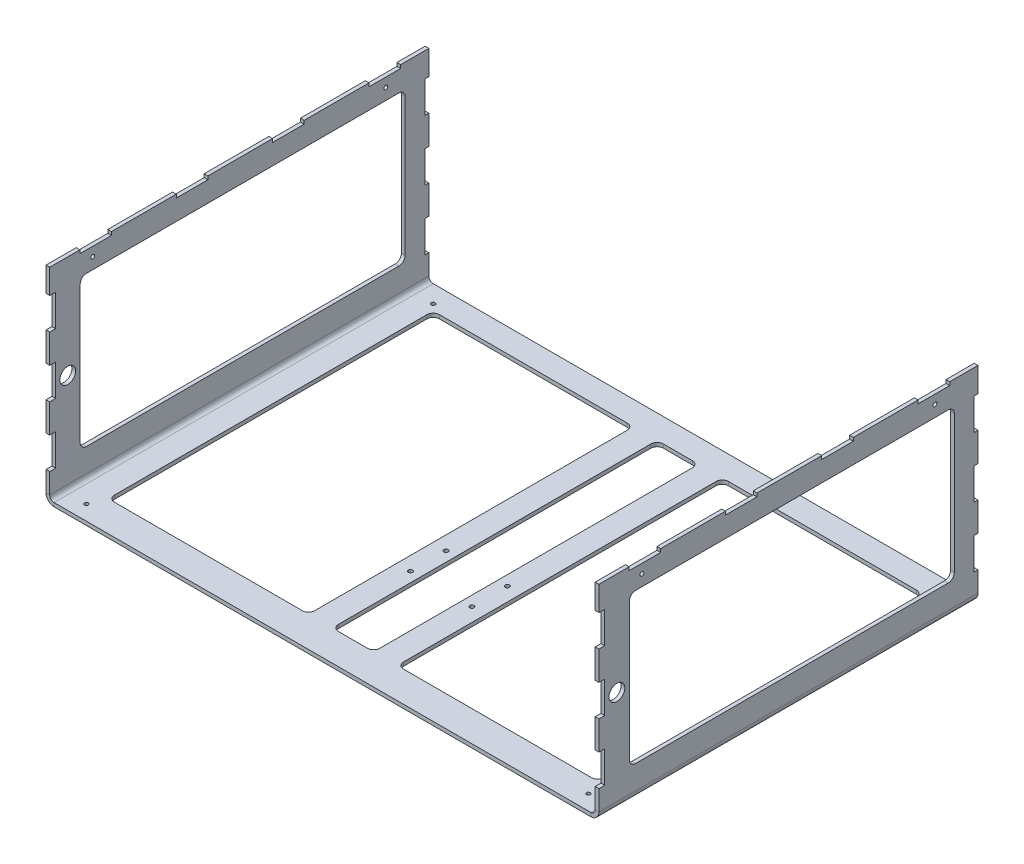
SolidWorks part; units mm, degrees
note: The reader was unsure of these and kept them because the rebuilt part matched: thickness of "Base-Flange1", "Edge-Flange1", "Edge-Flange2", "Sheet-Metal2", "Sheet-Metal3", "Sheet-Metal4", "Sheet-Metal5", "Sheet-Metal6", "Sheet-Metal11", "Sheet-Metal12", "Sheet-Metal13", "Sheet-Metal14", "Sheet-Metal15", "Sheet-Metal16", "Sheet-Metal17", "Sheet-Metal18", "Sheet-Metal21", "Sheet-Metal22"; flange length of "Edge-Flange1", "Edge-Flange2".
material "5052-H34"
ref_plane "Front Plane" through (0, 0, 0) normal (0, 0, 1) x (1, 0, 0)
ref_plane "Top Plane" through (0, 0, 0) normal (0, 1, 0) x (1, 0, 0)
ref_plane "Right Plane" through (0, 0, 0) normal (1, 0, 0) x (0, 0, -1)
sketch "Sketch1" plane through (0, 0, 0) normal (0, 1, 0) x (1, 0, 0)
  line L1 (-222.25, 152.4) -> (222.25, 152.4)
  line L2 (-222.25, 152.4) -> (-222.25, -152.4)
  line L3 (-222.25, -152.4) -> (222.25, -152.4)
  line L4 (222.25, 152.4) -> (222.25, -152.4)
  point P4 (0, 152.4)
  point P6 (222.25, 0)
  dimension "D1" = 444.5
  dimension "D2" = 304.8
base flange "Base-Flange1" sketch "Sketch1" thickness 3 reverse thickness direction no parameters "D1"=0.7366
edge flange "Edge-Flange1" sketch "Sketch11" flange angle 90 flange length 165.1 flange position material inside bend radius 3.5 thickness 3 relief rectangular parameters "D6"=10
sketch "Sketch11" plane through (-222.25, 0, 0) normal (-1, 0, 0) x (0, 0, 1)
  line L0 (-152.4, 0) -> (152.4, 0) construction
  line L1 (-152.4, 0) -> (152.4, 0)
  line L2 (-152.4, 0) -> (-152.4, 162.1)
  line L3 (-152.4, 162.1) -> (152.4, 162.1)
  line L4 (152.4, 162.1) -> (152.4, 0)
bend "EdgeBend1" bend radius 3.5 bend angle 90 parameters "D5"=1
edge flange "Edge-Flange2" sketch "Sketch14" flange angle 90 flange length 165.1 flange position material inside bend radius 3.5 thickness 3 relief rectangular parameters "D6"=10
sketch "Sketch14" plane through (222.25, 0, 0) normal (1, 0, 0) x (0, 0, -1)
  line L2 (-152.4, 0) -> (-152.4, 162.1)
  line L3 (-152.4, 162.1) -> (152.4, 162.1)
  line L4 (152.4, 162.1) -> (152.4, 0)
  line L7 (-152.4, 0) -> (152.4, 0) construction
  line L8 (-152.4, 0) -> (152.4, 0)
bend "EdgeBend2" bend radius 3.5 bend angle 90 parameters "D5"=2
sketch "Sketch17" plane through (0, 0, 0) normal (0, 1, 0) x (1, 0, 0)
  line L0 (-215.75, -152.4) -> (-215.75, 152.4) construction
  line L1 (-191.7, 133.35) -> (-40.7, 133.35)
  line L2 (-196.7, 128.35) -> (-196.7, -122.9)
  line L3 (-191.7, -127.9) -> (-40.7, -127.9)
  line L4 (196.7, 128.35) -> (196.7, -122.9)
  line L5 (215.75, 152.4) -> (215.75, -152.4) construction
  line L6 (215.75, 152.4) -> (-215.75, 152.4) construction
  line L7 (-215.75, -152.4) -> (215.75, -152.4) construction
  line L8 (-11.65, 133.35) -> (11.65, 133.35)
  line L10 (-35.7, 128.35) -> (-35.7, -122.9)
  line L12 (-16.65, 128.35) -> (-16.65, -122.9)
  line L14 (16.65, 128.35) -> (16.65, -122.9)
  line L16 (35.7, 128.35) -> (35.7, -122.9)
  line L17 (40.7, 133.35) -> (191.7, 133.35)
  line L18 (40.7, -127.9) -> (191.7, -127.9)
  line L19 (-11.65, -127.9) -> (11.65, -127.9)
  arc A0 (191.7, 133.35) -> (196.7, 128.35) centre (191.7, 128.35) cw
  arc A1 (191.7, -127.9) -> (196.7, -122.9) centre (191.7, -122.9) ccw
  arc A2 (40.7, -127.9) -> (35.7, -122.9) centre (40.7, -122.9) cw
  arc A3 (16.65, -122.9) -> (11.65, -127.9) centre (11.65, -122.9) cw
  arc A4 (-11.65, -127.9) -> (-16.65, -122.9) centre (-11.65, -122.9) cw
  arc A5 (-35.7, -122.9) -> (-40.7, -127.9) centre (-40.7, -122.9) cw
  arc A6 (-196.7, -122.9) -> (-191.7, -127.9) centre (-191.7, -122.9) ccw
  arc A7 (-191.7, 133.35) -> (-196.7, 128.35) centre (-191.7, 128.35) ccw
  arc A8 (-40.7, 133.35) -> (-35.7, 128.35) centre (-40.7, 128.35) cw
  arc A9 (-11.65, 133.35) -> (-16.65, 128.35) centre (-11.65, 128.35) ccw
  arc A10 (11.65, 133.35) -> (16.65, 128.35) centre (11.65, 128.35) cw
  arc A11 (40.7, 133.35) -> (35.7, 128.35) centre (40.7, 128.35) ccw
  point P26 (35.7, -127.9)
  point P31 (-16.65, -127.9)
  point P44 (16.65, 133.35)
  dimension "D9" = 5
  dimension "D1" = 19.05
  dimension "D2" = 19.05
  dimension "D3" = 19.05
  dimension "D4" = 24.5
  dimension "D5" = 19.05
  dimension "D6" = 19.05
  dimension "D7" = 161
  dimension "D8" = 161
extrude "Cut-Extrude1" cut sketch "Sketch17" against normal blind 10 normal cut yes
sketch "Sketch18" plane through (222.25, 0, 0) normal (1, 0, 0) x (0, 0, -1)
  line L0 (152.4, 3.5) -> (-152.4, 3.5) construction
  line L1 (-122.9, 143.05) -> (128.35, 143.05)
  line L2 (-127.9, 138.05) -> (-127.9, 27.55)
  line L3 (-122.9, 22.55) -> (128.35, 22.55)
  line L4 (133.35, 138.05) -> (133.35, 27.55)
  line L5 (152.4, 162.1) -> (-152.4, 162.1) construction
  line L6 (152.4, 3.5) -> (152.4, 162.1) construction
  line L7 (-152.4, 162.1) -> (-152.4, 3.5) construction
  arc A0 (128.35, 143.05) -> (133.35, 138.05) centre (128.35, 138.05) cw
  arc A1 (128.35, 22.55) -> (133.35, 27.55) centre (128.35, 27.55) ccw
  arc A2 (-127.9, 27.55) -> (-122.9, 22.55) centre (-122.9, 27.55) ccw
  arc A3 (-122.9, 143.05) -> (-127.9, 138.05) centre (-122.9, 138.05) ccw
  dimension "D5" = 5
  dimension "D1" = 19.05
  dimension "D2" = 19.05
  dimension "D3" = 19.05
  dimension "D4" = 24.5
extrude "Cut-Extrude2" cut sketch "Sketch18" against normal through all normal cut yes
sketch "Sketch19" plane through (0, 162.1, 0) normal (0, 1, 0) x (1, 0, 0)
  line L0 (222.25, 152.4) -> (222.25, -152.4) construction
  line L1 (222.25, 129.7) -> (218.4302, 129.7)
  line L2 (222.25, 129.7) -> (222.25, 104.3)
  line L3 (222.25, 104.3) -> (218.4302, 104.3)
  line L4 (218.4302, 129.7) -> (218.4302, 104.3)
  line L5 (222.25, 152.4) -> (219.25, 152.4) construction
  line L6 (219.25, 51.9667) -> (222.25, 51.9667) construction
  line L7 (218.4302, 52.1667) -> (222.25, 52.1667)
  line L8 (218.4302, 52.1667) -> (218.4302, 26.7667)
  line L9 (218.4302, 26.7667) -> (222.25, 26.7667)
  line L10 (222.25, 52.1667) -> (222.25, 26.7667)
  line L11 (219.25, -127.9) -> (222.25, -127.9) construction
  line L12 (219.25, -102.9) -> (222.25, -102.9) construction
  line L13 (219.25, -50.4666) -> (222.25, -50.4666) construction
  line L14 (219.25, -25.4666) -> (222.25, -25.4666) construction
  line L15 (219.25, 26.9667) -> (222.25, 26.9667) construction
  line L16 (219.25, -127.9) -> (222.25, -127.9) construction
  line L17 (219.25, -102.9) -> (222.25, -102.9) construction
  line L18 (219.25, -50.4666) -> (222.25, -50.4666) construction
  line L19 (219.25, -25.4666) -> (222.25, -25.4666) construction
  line L20 (219.25, 26.9667) -> (222.25, 26.9667) construction
  line L21 (219.25, 51.9667) -> (222.25, 51.9667) construction
  line L23 (216.9384, -25.2666) -> (222.25, -25.2666)
  line L24 (216.9384, -25.2666) -> (216.9384, -50.6666)
  line L25 (216.9384, -50.6666) -> (222.25, -50.6666)
  line L26 (222.25, -25.2666) -> (222.25, -50.6666)
  line L27 (215.9677, -102.7) -> (222.25, -102.7)
  line L28 (215.9677, -102.7) -> (215.9677, -128.1)
  line L29 (215.9677, -128.1) -> (222.25, -128.1)
  line L30 (222.25, -102.7) -> (222.25, -128.1)
  dimension "D1" = 22.7
  dimension "D2" = 25.4
  dimension "D3" = 0.2
  dimension "D4" = 0.2
  dimension "D5" = 0.2
  dimension "D6" = 0.2
  dimension "D7" = 0.2
  dimension "D8" = 0.2
extrude "Cut-Extrude3" cut sketch "Sketch19" against normal blind 2.7 normal cut yes
mirror "Mirror1" about plane through (0, 0, 0) normal (1, 0, 0) of "Cut-Extrude3"
sketch "Sketch20" plane through (222.25, 0, 0) normal (1, 0, 0) x (0, 0, -1)
  line L0 (-127.9, 79.55) -> (-137.9, 79.55) construction
  line L1 (-137.9, -3) -> (-137.9, 162.1) construction
  line L2 (152.4, -3) -> (-152.4, -3) construction
  line L3 (-127.9, 138.05) -> (-127.9, 27.55) construction
  line L4 (-128.1, 162.1) -> (-152.4, 162.1) construction
  circle A0 centre (-137.9, 79.55) radius 6.35
  dimension "D1" = 12.7
  dimension "D2" = 10
extrude "Cut-Extrude4" cut sketch "Sketch20" against normal through all normal cut yes
sketch "Sketch21" plane through (0, 0, 152.4) normal (0, 0, 1) x (1, 0, 0)
  line L0 (-219.25, 20) -> (-222.25, 20) construction
  line L1 (-222.25, 45) -> (-219.25, 45) construction
  line L2 (-219.25, 68.55) -> (-222.25, 68.55) construction
  line L3 (-222.25, 93.55) -> (-219.25, 93.55) construction
  line L4 (-219.25, 117.1) -> (-222.25, 117.1) construction
  line L5 (-222.25, 142.1) -> (-219.25, 142.1) construction
  line L6 (-219.25, 20) -> (-222.25, 20) construction
  line L7 (-222.25, 45) -> (-219.25, 45) construction
  line L8 (-219.25, 68.55) -> (-222.25, 68.55) construction
  line L9 (-222.25, 93.55) -> (-219.25, 93.55) construction
  line L10 (-219.25, 117.1) -> (-222.25, 117.1) construction
  line L11 (-222.25, 142.1) -> (-219.25, 142.1) construction
  line L13 (-227.6486, 142.35) -> (-210.1841, 142.35)
  line L14 (-227.6486, 142.35) -> (-227.6486, 116.95)
  line L15 (-227.6486, 116.95) -> (-210.1841, 116.95)
  line L16 (-210.1841, 142.35) -> (-210.1841, 116.95)
  line L17 (-227.6486, 93.75) -> (-214.0015, 93.75)
  line L18 (-227.6486, 93.75) -> (-227.6486, 68.35)
  line L19 (-227.6486, 68.35) -> (-214.0015, 68.35)
  line L20 (-214.0015, 93.75) -> (-214.0015, 68.35)
  line L21 (-226.7516, 45.2) -> (-212.8029, 45.2)
  line L22 (-226.7516, 45.2) -> (-226.7516, 19.8)
  line L23 (-226.7516, 19.8) -> (-212.8029, 19.8)
  line L24 (-212.8029, 45.2) -> (-212.8029, 19.8)
  point P24 (-220.75, 45)
  dimension "D1" = 25.4
  dimension "D2" = 0.3
  dimension "D3" = 25.4
  dimension "D4" = 0.2
  dimension "D5" = 0.2
  dimension "D6" = 0.2
extrude "Cut-Extrude5" cut sketch "Sketch21" against normal blind 4.7 normal cut yes
mirror "Mirror2" about plane through (0, 0, 0) normal (1, 0, 0) of "Cut-Extrude5"
mirror "Mirror3" about plane through (0, 0, 0) normal (0, 0, 1) of "Mirror2", "Cut-Extrude5"
sketch "Sketch22" plane through (0, 0, -147.7) normal (0, 0, -1) x (-1, 0, 0)
  line L4 (-222.25, 142.35) -> (-222.25, 116.95)
  line L5 (-222.25, 116.95) -> (-219.25, 116.95)
  line L6 (-219.25, 116.95) -> (-219.25, 142.35)
  line L7 (-219.25, 142.35) -> (-222.25, 142.35)
  line L8 (-222.25, 142.35) -> (-222.25, 116.95)
  line L9 (-222.25, 116.95) -> (-219.25, 116.95)
  line L10 (-219.25, 116.95) -> (-219.25, 142.35)
  line L11 (-219.25, 142.35) -> (-222.25, 142.35)
  line L12 (-222.25, 93.75) -> (-222.25, 68.35)
  line L13 (-222.25, 68.35) -> (-219.25, 68.35)
  line L14 (-219.25, 68.35) -> (-219.25, 93.75)
  line L15 (-219.25, 93.75) -> (-222.25, 93.75)
  line L16 (-222.25, 93.75) -> (-222.25, 68.35)
  line L17 (-222.25, 68.35) -> (-219.25, 68.35)
  line L18 (-219.25, 68.35) -> (-219.25, 93.75)
  line L19 (-219.25, 93.75) -> (-222.25, 93.75)
  line L20 (-222.25, 45.2) -> (-222.25, 19.8)
  line L21 (-222.25, 19.8) -> (-219.25, 19.8)
  line L22 (-219.25, 19.8) -> (-219.25, 45.2)
  line L23 (-219.25, 45.2) -> (-222.25, 45.2)
  line L24 (-222.25, 45.2) -> (-222.25, 19.8)
  line L25 (-222.25, 19.8) -> (-219.25, 19.8)
  line L26 (-219.25, 19.8) -> (-219.25, 45.2)
  line L27 (-219.25, 45.2) -> (-222.25, 45.2)
  line L48 (222.25, 19.8) -> (222.25, 45.2) construction
  line L49 (222.25, 45.2) -> (219.25, 45.2) construction
  line L50 (219.25, 45.2) -> (219.25, 19.8) construction
  line L51 (219.25, 19.8) -> (222.25, 19.8) construction
  line L52 (222.25, 68.35) -> (222.25, 93.75) construction
  line L53 (222.25, 93.75) -> (219.25, 93.75) construction
  line L54 (219.25, 93.75) -> (219.25, 68.35) construction
  line L55 (219.25, 68.35) -> (222.25, 68.35) construction
  line L56 (222.25, 116.95) -> (222.25, 142.35) construction
  line L57 (222.25, 142.35) -> (219.25, 142.35) construction
  line L58 (219.25, 142.35) -> (219.25, 116.95) construction
  line L59 (219.25, 116.95) -> (222.25, 116.95) construction
  line L60 (222.25, 19.8) -> (222.25, 45.2)
  line L61 (222.25, 45.2) -> (219.25, 45.2)
  line L62 (219.25, 45.2) -> (219.25, 19.8)
  line L63 (219.25, 19.8) -> (222.25, 19.8)
  line L64 (222.25, 68.35) -> (222.25, 93.75)
  line L65 (222.25, 93.75) -> (219.25, 93.75)
  line L66 (219.25, 93.75) -> (219.25, 68.35)
  line L67 (219.25, 68.35) -> (222.25, 68.35)
  line L68 (222.25, 116.95) -> (222.25, 142.35)
  line L69 (222.25, 142.35) -> (219.25, 142.35)
  line L70 (219.25, 142.35) -> (219.25, 116.95)
  line L71 (219.25, 116.95) -> (222.25, 116.95)
  dimension "D1" = 0
  dimension "D2" = 0
  dimension "D3" = 0
extrude "Boss-Extrude1" add sketch "Sketch22" along normal blind 1.5
sketch "Sketch23" plane through (0, 0, 0) normal (0, 1, 0) x (1, 0, 0)
  circle A4 centre (24.68, -56.9) radius 1.7
  circle A5 centre (24.68, -28.4) radius 1.7
  circle A6 centre (-24.6834, -56.9) radius 1.7
  circle A7 centre (-24.6834, -28.4) radius 1.7
extrude "Cut-Extrude6" cut sketch "Sketch23" against normal blind 10 normal cut yes
sketch "Sketch24" plane through (222.25, 0, 0) normal (1, 0, 0) x (0, 0, -1)
  circle A2 centre (117.8, 152.1) radius 1.55
  circle A3 centre (-117.8, 152.1) radius 1.55
extrude "Cut-Extrude7" cut sketch "Sketch24" against normal through all normal cut yes
sketch "Sketch25" plane through (0, 0, 0) normal (0, 1, 0) x (1, 0, 0)
  line L0 (-215.75, 0) -> (-201.75, 0) construction
  line L1 (-215.75, -152.4) -> (-215.75, 152.4) construction
  line L2 (-201.75, 0) -> (-201.75, 138.375) construction
  line L4 (215.75, 152.4) -> (-215.75, 152.4) construction
  line L5 (-201.75, 0) -> (-201.75, -140.375) construction
  line L6 (-215.75, -152.4) -> (215.75, -152.4) construction
  line L7 (0, 181.2656) -> (0, -232.1381) construction
  circle A0 centre (-201.75, 138.375) radius 1.55
  circle A1 centre (-201.75, -140.375) radius 1.5
  circle A2 centre (201.75, 138.375) radius 1.55
  circle A3 centre (201.75, -140.375) radius 1.5
  dimension "D3" = 3.1
  dimension "D5" = 3
  dimension "D1" = 14
  dimension "D2" = 14.025
  dimension "D4" = 12.025
extrude "Cut-Extrude8" cut sketch "Sketch25" against normal through all normal cut yes
sketch "Bend-Lines1" [suppressed] plane through (0, 0, 0) normal (0, 1, 0) x (1, 0, 0)
sketch "Bounding-Box1" [suppressed] plane through (0, 0, 0) normal (0, 1, 0) x (1, 0, 0)
sheet metal parameters "Sheet-Metal2" thickness 3 parameters "D1"=0.7366, "D7"=2.5
flat pattern "Flat-Pattern2" [suppressed]
sketch "Bend-Lines2" plane through (0, 0, 0) normal (0, 1, 0) x (1, 0, 0)
sketch3d "Bounding-Box2" [suppressed]
  line L0 (222.25, -152.4, 0) -> (-222.25, -152.4, 0) construction
  line L1 (222.25, 152.4, 0) -> (-222.25, 152.4, 0) construction
  line L2 (222.25, -152.4, 0) -> (222.25, 152.4, 0) construction
  line L3 (-222.25, -152.4, 0) -> (-222.25, 152.4, 0) construction
sheet metal parameters "Sheet-Metal3" thickness 3 parameters "D1"=0.7366, "D7"=2.5
flat pattern "Flat-Pattern2"
sketch "Bend-Lines2" plane through (0, 0, 0) normal (0, 1, 0) x (1, 0, 0)
  line L0 (-219.9309, 152.4) -> (-219.9309, -152.4) construction
  line L1 (-219.9309, 152.4) -> (-219.9309, -152.4) construction
sketch3d "Bounding-Box2" [suppressed]
  line L0 (222.25, -152.4, 0) -> (-382.7117, -152.4, 0) construction
  line L1 (222.25, 152.4, 0) -> (-382.7117, 152.4, 0) construction
  line L2 (222.25, -152.4, 0) -> (222.25, 152.4, 0) construction
  line L3 (-382.7117, -152.4, 0) -> (-382.7117, 152.4, 0) construction
bend of the flat pattern "Flatten-<EdgeBend1>1"
sheet metal parameters "Sheet-Metal4" thickness 3 parameters "D1"=0.7366, "D7"=2.5
flat pattern "Flat-Pattern2"
sketch "Bend-Lines2" plane through (0, 0, 0) normal (0, 1, 0) x (1, 0, 0)
  line L0 (-219.1666, 152.4) -> (-219.1666, -152.4) construction
  line L1 (-219.1666, 152.4) -> (-219.1666, -152.4) construction
  line L2 (219.1666, -152.4) -> (219.1666, 152.4) construction
  line L3 (219.1666, -152.4) -> (219.1666, 152.4) construction
sketch3d "Bounding-Box2" [suppressed]
  line L0 (381.1832, -152.4, 0) -> (-381.1832, -152.4, 0) construction
  line L1 (381.1832, 152.4, 0) -> (-381.1832, 152.4, 0) construction
  line L2 (381.1832, -152.4, 0) -> (381.1832, 152.4, 0) construction
  line L3 (-381.1832, -152.4, 0) -> (-381.1832, 152.4, 0) construction
bend of the flat pattern "Flatten-<EdgeBend1>1"
bend of the flat pattern "Flatten-<EdgeBend2>1"
sheet metal parameters "Sheet-Metal5" thickness 3 parameters "D1"=0.7366, "D7"=2.5
flat pattern "Flat-Pattern2"
sketch "Bend-Lines2" plane through (0, 0, 0) normal (0, 1, 0) x (1, 0, 0)
  line L0 (-219.1666, 152.4) -> (-219.1666, -152.4) construction
  line L1 (-219.1666, 152.4) -> (-219.1666, -152.4) construction
  line L2 (219.1666, -152.4) -> (219.1666, 152.4) construction
  line L3 (219.1666, -152.4) -> (219.1666, 152.4) construction
sketch3d "Bounding-Box2" [suppressed]
  line L0 (381.1832, -152.4, 0) -> (-381.1832, -152.4, 0) construction
  line L1 (381.1832, 152.4, 0) -> (-381.1832, 152.4, 0) construction
  line L2 (381.1832, -152.4, 0) -> (381.1832, 152.4, 0) construction
  line L3 (-381.1832, -152.4, 0) -> (-381.1832, 152.4, 0) construction
bend of the flat pattern "Flatten-<EdgeBend1>1"
bend of the flat pattern "Flatten-<EdgeBend2>1"
sheet metal parameters "Sheet-Metal6" thickness 3 parameters "D1"=0.7366, "D7"=2.5
flat pattern "Flat-Pattern2"
sketch "Bend-Lines2" plane through (0, 0, 0) normal (0, 1, 0) x (1, 0, 0)
  line L0 (-219.4885, 152.4) -> (-219.4885, -152.4) construction
  line L1 (-219.4885, 152.4) -> (-219.4885, -152.4) construction
  line L2 (219.4885, -152.4) -> (219.4885, 152.4) construction
  line L3 (219.4885, -152.4) -> (219.4885, 152.4) construction
sketch3d "Bounding-Box2" [suppressed]
  line L0 (381.827, -152.4, 0) -> (-381.827, -152.4, 0) construction
  line L1 (381.827, 152.4, 0) -> (-381.827, 152.4, 0) construction
  line L2 (381.827, -152.4, 0) -> (381.827, 152.4, 0) construction
  line L3 (-381.827, -152.4, 0) -> (-381.827, 152.4, 0) construction
bend of the flat pattern "Flatten-<EdgeBend1>1"
bend of the flat pattern "Flatten-<EdgeBend2>1"
sheet metal parameters "Sheet-Metal11" thickness 3 parameters "D1"=0.7366, "D7"=2.5
flat pattern "Flat-Pattern2"
sketch "Bend-Lines2" plane through (0, 0, 0) normal (0, 1, 0) x (1, 0, 0)
  line L0 (-219.4885, 152.4) -> (-219.4885, -152.4) construction
  line L1 (-219.4885, 152.4) -> (-219.4885, -152.4) construction
  line L2 (219.4885, -152.4) -> (219.4885, 152.4) construction
  line L3 (219.4885, -152.4) -> (219.4885, 152.4) construction
sketch3d "Bounding-Box2" [suppressed]
  line L0 (381.827, -152.4, 0) -> (-381.827, -152.4, 0) construction
  line L1 (381.827, 152.4, 0) -> (-381.827, 152.4, 0) construction
  line L2 (381.827, -152.4, 0) -> (381.827, 152.4, 0) construction
  line L3 (-381.827, -152.4, 0) -> (-381.827, 152.4, 0) construction
bend of the flat pattern "Flatten-<EdgeBend1>1"
bend of the flat pattern "Flatten-<EdgeBend2>1"
sheet metal parameters "Sheet-Metal12" thickness 3 parameters "D1"=0.7366, "D7"=2.5
flat pattern "Flat-Pattern2"
sketch "Bend-Lines2" plane through (0, 0, 0) normal (0, 1, 0) x (1, 0, 0)
  line L0 (-219.4885, 152.4) -> (-219.4885, -152.4) construction
  line L1 (-219.4885, 152.4) -> (-219.4885, -152.4) construction
  line L2 (219.4885, -152.4) -> (219.4885, 152.4) construction
  line L3 (219.4885, -152.4) -> (219.4885, 152.4) construction
sketch3d "Bounding-Box2" [suppressed]
  line L0 (381.827, -152.4, 0) -> (-381.827, -152.4, 0) construction
  line L1 (381.827, 152.4, 0) -> (-381.827, 152.4, 0) construction
  line L2 (381.827, -152.4, 0) -> (381.827, 152.4, 0) construction
  line L3 (-381.827, -152.4, 0) -> (-381.827, 152.4, 0) construction
bend of the flat pattern "Flatten-<EdgeBend1>1"
bend of the flat pattern "Flatten-<EdgeBend2>1"
sheet metal parameters "Sheet-Metal13" thickness 3 parameters "D1"=0.7366, "D7"=2.5
flat pattern "Flat-Pattern2"
sketch "Bend-Lines2" plane through (0, 0, 0) normal (0, 1, 0) x (1, 0, 0)
  line L0 (-219.4885, 152.4) -> (-219.4885, -152.4) construction
  line L1 (-219.4885, 152.4) -> (-219.4885, -152.4) construction
  line L2 (219.4885, -152.4) -> (219.4885, 152.4) construction
  line L3 (219.4885, -152.4) -> (219.4885, 152.4) construction
sketch3d "Bounding-Box2" [suppressed]
  line L0 (381.827, -152.4, 0) -> (-381.827, -152.4, 0) construction
  line L1 (381.827, 152.4, 0) -> (-381.827, 152.4, 0) construction
  line L2 (381.827, -152.4, 0) -> (381.827, 152.4, 0) construction
  line L3 (-381.827, -152.4, 0) -> (-381.827, 152.4, 0) construction
bend of the flat pattern "Flatten-<EdgeBend1>1"
bend of the flat pattern "Flatten-<EdgeBend2>1"
sheet metal parameters "Sheet-Metal14" thickness 3 parameters "D1"=0.7366, "D7"=2.5
flat pattern "Flat-Pattern2"
sketch "Bend-Lines2" plane through (0, 0, 0) normal (0, 1, 0) x (1, 0, 0)
  line L0 (-219.4885, 152.4) -> (-219.4885, -152.4) construction
  line L1 (-219.4885, 152.4) -> (-219.4885, -152.4) construction
  line L2 (219.4885, -152.4) -> (219.4885, 152.4) construction
  line L3 (219.4885, -152.4) -> (219.4885, 152.4) construction
sketch3d "Bounding-Box2" [suppressed]
  line L0 (381.827, -152.4, 0) -> (-381.827, -152.4, 0) construction
  line L1 (381.827, 152.4, 0) -> (-381.827, 152.4, 0) construction
  line L2 (381.827, -152.4, 0) -> (381.827, 152.4, 0) construction
  line L3 (-381.827, -152.4, 0) -> (-381.827, 152.4, 0) construction
bend of the flat pattern "Flatten-<EdgeBend1>1"
bend of the flat pattern "Flatten-<EdgeBend2>1"
sheet metal parameters "Sheet-Metal15" thickness 3 parameters "D1"=0.7366, "D7"=2.5
flat pattern "Flat-Pattern2"
sketch "Bend-Lines2" plane through (0, 0, 0) normal (0, 1, 0) x (1, 0, 0)
  line L0 (-219.4885, 152.4) -> (-219.4885, -152.4) construction
  line L1 (-219.4885, 152.4) -> (-219.4885, -152.4) construction
  line L2 (219.4885, -152.4) -> (219.4885, 152.4) construction
  line L3 (219.4885, -152.4) -> (219.4885, 152.4) construction
sketch3d "Bounding-Box2" [suppressed]
  line L0 (381.827, -152.4, 0) -> (-381.827, -152.4, 0) construction
  line L1 (381.827, 152.4, 0) -> (-381.827, 152.4, 0) construction
  line L2 (381.827, -152.4, 0) -> (381.827, 152.4, 0) construction
  line L3 (-381.827, -152.4, 0) -> (-381.827, 152.4, 0) construction
bend of the flat pattern "Flatten-<EdgeBend1>1"
bend of the flat pattern "Flatten-<EdgeBend2>1"
sheet metal parameters "Sheet-Metal16" thickness 3 parameters "D1"=0.7366, "D7"=2.5
flat pattern "Flat-Pattern2"
sketch "Bend-Lines2" plane through (0, 0, 0) normal (0, 1, 0) x (1, 0, 0)
  line L0 (-219.4885, 152.4) -> (-219.4885, -152.4) construction
  line L1 (-219.4885, 152.4) -> (-219.4885, -152.4) construction
  line L2 (219.4885, -152.4) -> (219.4885, 152.4) construction
  line L3 (219.4885, -152.4) -> (219.4885, 152.4) construction
sketch3d "Bounding-Box2" [suppressed]
  line L0 (381.827, -152.4, 0) -> (-381.827, -152.4, 0) construction
  line L1 (381.827, 152.4, 0) -> (-381.827, 152.4, 0) construction
  line L2 (381.827, -152.4, 0) -> (381.827, 152.4, 0) construction
  line L3 (-381.827, -152.4, 0) -> (-381.827, 152.4, 0) construction
bend of the flat pattern "Flatten-<EdgeBend1>1"
bend of the flat pattern "Flatten-<EdgeBend2>1"
sheet metal parameters "Sheet-Metal17" thickness 3 parameters "D1"=0.7366, "D7"=2.5
flat pattern "Flat-Pattern2"
sketch "Bend-Lines2" plane through (0, 0, 0) normal (0, 1, 0) x (1, 0, 0)
  line L0 (-219.4885, 152.4) -> (-219.4885, -152.4) construction
  line L1 (-219.4885, 152.4) -> (-219.4885, -152.4) construction
  line L2 (219.4885, -152.4) -> (219.4885, 152.4) construction
  line L3 (219.4885, -152.4) -> (219.4885, 152.4) construction
sketch3d "Bounding-Box2" [suppressed]
  line L0 (381.827, -152.4, 0) -> (-381.827, -152.4, 0) construction
  line L1 (381.827, 152.4, 0) -> (-381.827, 152.4, 0) construction
  line L2 (381.827, -152.4, 0) -> (381.827, 152.4, 0) construction
  line L3 (-381.827, -152.4, 0) -> (-381.827, 152.4, 0) construction
bend of the flat pattern "Flatten-<EdgeBend1>1"
bend of the flat pattern "Flatten-<EdgeBend2>1"
sheet metal parameters "Sheet-Metal18" thickness 3 parameters "D1"=0.7366, "D7"=2.5
flat pattern "Flat-Pattern2"
sketch "Bend-Lines2" plane through (0, 0, 0) normal (0, 1, 0) x (1, 0, 0)
  line L0 (-219.4885, 152.4) -> (-219.4885, -152.4) construction
  line L1 (-219.4885, 152.4) -> (-219.4885, -152.4) construction
  line L2 (219.4885, -152.4) -> (219.4885, 152.4) construction
  line L3 (219.4885, -152.4) -> (219.4885, 152.4) construction
sketch3d "Bounding-Box2" [suppressed]
  line L0 (381.827, -152.4, 0) -> (-381.827, -152.4, 0) construction
  line L1 (381.827, 152.4, 0) -> (-381.827, 152.4, 0) construction
  line L2 (381.827, -152.4, 0) -> (381.827, 152.4, 0) construction
  line L3 (-381.827, -152.4, 0) -> (-381.827, 152.4, 0) construction
bend of the flat pattern "Flatten-<EdgeBend1>1"
bend of the flat pattern "Flatten-<EdgeBend2>1"
sheet metal parameters "Sheet-Metal21" thickness 3 parameters "D1"=0.7366, "D7"=2.5
flat pattern "Flat-Pattern2"
sketch "Bend-Lines2" plane through (0, 0, 0) normal (0, 1, 0) x (1, 0, 0)
  line L0 (-219.4885, 152.4) -> (-219.4885, -152.4) construction
  line L1 (-219.4885, 152.4) -> (-219.4885, -152.4) construction
  line L2 (219.4885, -152.4) -> (219.4885, 152.4) construction
  line L3 (219.4885, -152.4) -> (219.4885, 152.4) construction
sketch3d "Bounding-Box2" [suppressed]
  line L0 (381.827, -152.4, 0) -> (-381.827, -152.4, 0) construction
  line L1 (381.827, 152.4, 0) -> (-381.827, 152.4, 0) construction
  line L2 (381.827, -152.4, 0) -> (381.827, 152.4, 0) construction
  line L3 (-381.827, -152.4, 0) -> (-381.827, 152.4, 0) construction
bend of the flat pattern "Flatten-<EdgeBend1>1"
bend of the flat pattern "Flatten-<EdgeBend2>1"
sheet metal parameters "Sheet-Metal22" thickness 3 parameters "D1"=0.7366, "D7"=2.5
flat pattern "Flat-Pattern2"
sketch "Bend-Lines2" plane through (0, 0, 0) normal (0, 1, 0) x (1, 0, 0)
  line L0 (-219.4885, 152.4) -> (-219.4885, -152.4) construction
  line L1 (-219.4885, 152.4) -> (-219.4885, -152.4) construction
  line L2 (219.4885, -152.4) -> (219.4885, 152.4) construction
  line L3 (219.4885, -152.4) -> (219.4885, 152.4) construction
sketch3d "Bounding-Box2" [suppressed]
  line L0 (381.827, -152.4, 0) -> (-381.827, -152.4, 0) construction
  line L1 (381.827, 152.4, 0) -> (-381.827, 152.4, 0) construction
  line L2 (381.827, -152.4, 0) -> (381.827, 152.4, 0) construction
  line L3 (-381.827, -152.4, 0) -> (-381.827, 152.4, 0) construction
bend of the flat pattern "Flatten-<EdgeBend1>1"
bend of the flat pattern "Flatten-<EdgeBend2>1"
